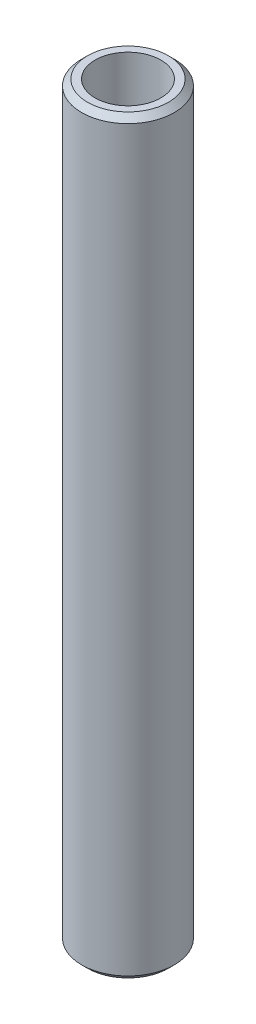
SolidWorks part; units mm, degrees
ref_plane "Front Plane" through (0, 0, 0) normal (0, 0, 1) x (1, 0, 0)
ref_plane "Top Plane" through (0, 0, 0) normal (0, 1, 0) x (1, 0, 0)
ref_plane "Right Plane" through (0, 0, 0) normal (1, 0, 0) x (0, 0, -1)
sketch "Sketch1" plane through (0, 0, 0) normal (0, 1, 0) x (1, 0, 0)
  circle A0 centre (0, 0) radius 20
  dimension "SHAFT_OD" = 40
extrude "Boss-Extrude1" add sketch "Sketch1" along normal blind 323.7128
sketch "Sketch2" plane through (0, 0, 0) normal (0, 1, 0) x (1, 0, 0)
  circle A0 centre (0, 0) radius 14.1912
  dimension "BORE_D" = 28.3823
extrude "Cut-Extrude1" cut sketch "Sketch2" along normal through all
chamfer "Chamfer1" distance 2.5641 angle 45 2 edges at (0, 323.7128, 20) (0, 0, 20)
